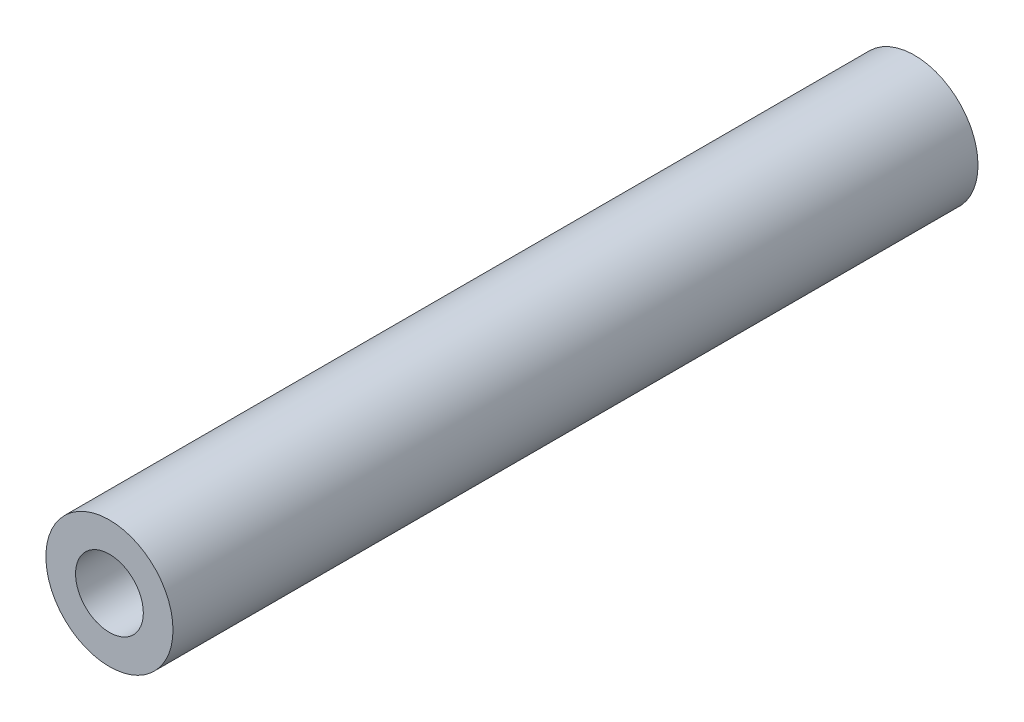
SolidWorks part; units mm, degrees
note: '?' marks a value the reader was unsure of.
material "Rubber"
ref_plane "Front Plane" through (0, 0, 0) normal (0, 0, 1) x (1, 0, 0)
ref_plane "Top Plane" through (0, 0, 0) normal (0, 1, 0) x (1, 0, 0)
ref_plane "Right Plane" through (0, 0, 0) normal (1, 0, 0) x (0, 0, -1)
ref_axis "X" through (-88.99, 0, 0) along (1, 0, 0)?
ref_axis "Y" through (0, 55, 0) along (0, -1, 0)?
ref_axis "Z" through (0, 0, -88.99) along (0, 0, 1)?
sketch "Sketch1" plane through (0, 0, 0) normal (0, 0, 1) x (1, 0, 0)
  circle A0 centre (0, 0) radius 1.5 construction
  circle A1 centre (0, 0) radius 3
  dimension "D1" = 3
  dimension "D2" = 6
extrude "Boss-Extrude1" add sketch "Sketch1" along normal mid plane 38
sketch "Sketch5" plane through (0, 0, 19) normal (0, 0, 1) x (1, 0, 0)
  point P0 (0, 0)
hole_wizard "M3 Clearance Hole" positions "Sketch5" profile "Sketch4" hole size "M3" standard "ANSI Metric" end condition through all
sketch "Sketch4" plane through (0, 0, 19) normal (1, 0, 0) x (0, -1, 0)
  line L0 (0, 0) -> (0, 38)
  line L1 (0, 38) -> (1.6, 38)
  line L2 (1.6, 38) -> (1.6, 0)
  line L5 (1.6, 0) -> (0, 0)
  line L11 (0, -6.35) -> (0, 107.95) construction
  dimension "Thru Hole Dia." = 3.2
  dimension "Thru Hole Depth" = 38
sketch "Sketch2" plane through (0, 0, 0) normal (0, 0, 1) x (1, 0, 0)
  line L0 (0, 0) -> (8, 0) construction
  line L1 (4, 1.5) -> (4, -1.5) construction
  circle A0 centre (8, 0) radius 1.5 construction
  circle A1 centre (8, 0) radius 3
  circle A3 centre (0, 0) radius 3 construction
  circle A4 centre (0, 0) radius 1.5 construction
  arc A5 (1.9726, 2.2603) -> (6.0274, 2.2603) centre (4, 4.5833) ccw
  arc A6 (1.9726, -2.2603) -> (6.0274, -2.2603) centre (4, -4.5833) cw
  circle A7 centre (0, 0) radius 3
  dimension "D1" = 3
  dimension "D2" = 8
extrude "Boss-Extrude2" [suppressed] add sketch "Sketch2" along normal up to surface and the other way up to surface contours A1 | A7 A6 A1 A5
sketch "Sketch8" plane through (0, 0, 19) normal (0, 0, 1) x (1, 0, 0)
  point P0 (8, 0)
hole_wizard "M3 Clearance Hole2" [suppressed] positions "Sketch8" profile "Sketch7" hole size "M3" standard "ANSI Metric"
sketch "Sketch7" plane through (10, 0, 19) normal (1, 0, 0) x (0, -1, 0)
  line L0 (0, 0) -> (0, 38)
  line L1 (0, 38) -> (1.6, 38)
  line L2 (1.6, 38) -> (1.6, 0)
  line L5 (1.6, 0) -> (0, 0)
  line L11 (0, -6.35) -> (0, 107.95) construction
  dimension "Thru Hole Dia." = 3.2
  dimension "Thru Hole Depth" = 38
equation "\"Spacing\" = 8mm"
equation "\"D2@Sketch2\"=\"Spacing\""
